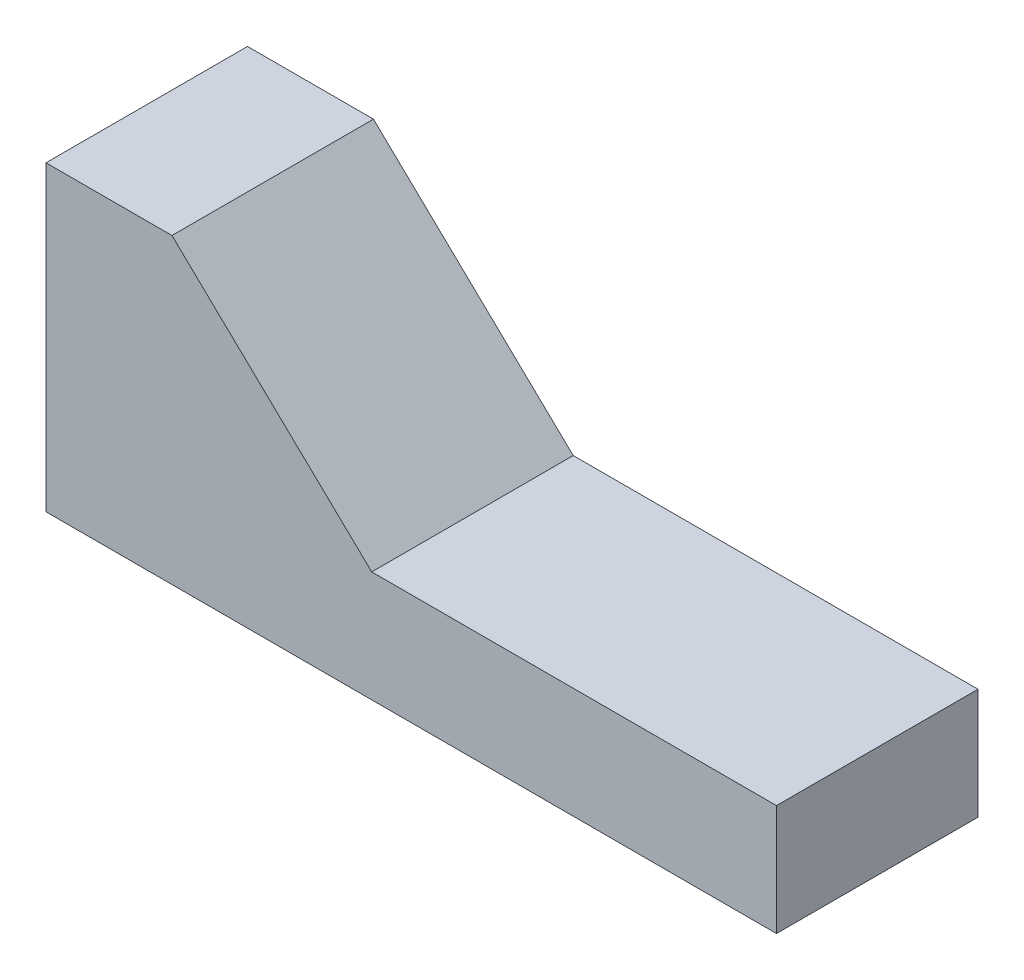
SolidWorks part; units mm, degrees
ref_plane "Front Plane" through (0, 0, 0) normal (0, 0, 1) x (1, 0, 0)
ref_plane "Top Plane" through (0, 0, 0) normal (0, 1, 0) x (1, 0, 0)
ref_plane "Right Plane" through (0, 0, 0) normal (1, 0, 0) x (0, 0, -1)
sketch "Sketch1" plane through (0, 0, 0) normal (0, 0, 1) x (1, 0, 0)
  line L0 (-72.5, 30) -> (-47.5, 30)
  line L1 (-47.5, 30) -> (-7.8445, -8)
  line L2 (-7.8445, -8) -> (72.5, -8)
  line L3 (72.5, -8) -> (72.5, -30)
  line L4 (72.5, -30) -> (-72.5, -30)
  line L5 (-72.5, -30) -> (-72.5, 30)
  point P6 (-47.5, -8)
  point P8 (0, 0)
  point P9 (-7.8445, -8)
  dimension "D2" = 145
  dimension "D3" = 60
  dimension "D4" = 38
  dimension "D5" = 30
  dimension "D6" = 72.5
extrude "Boss-Extrude1" add sketch "Sketch1" along normal blind 20 and the other way blind 20
